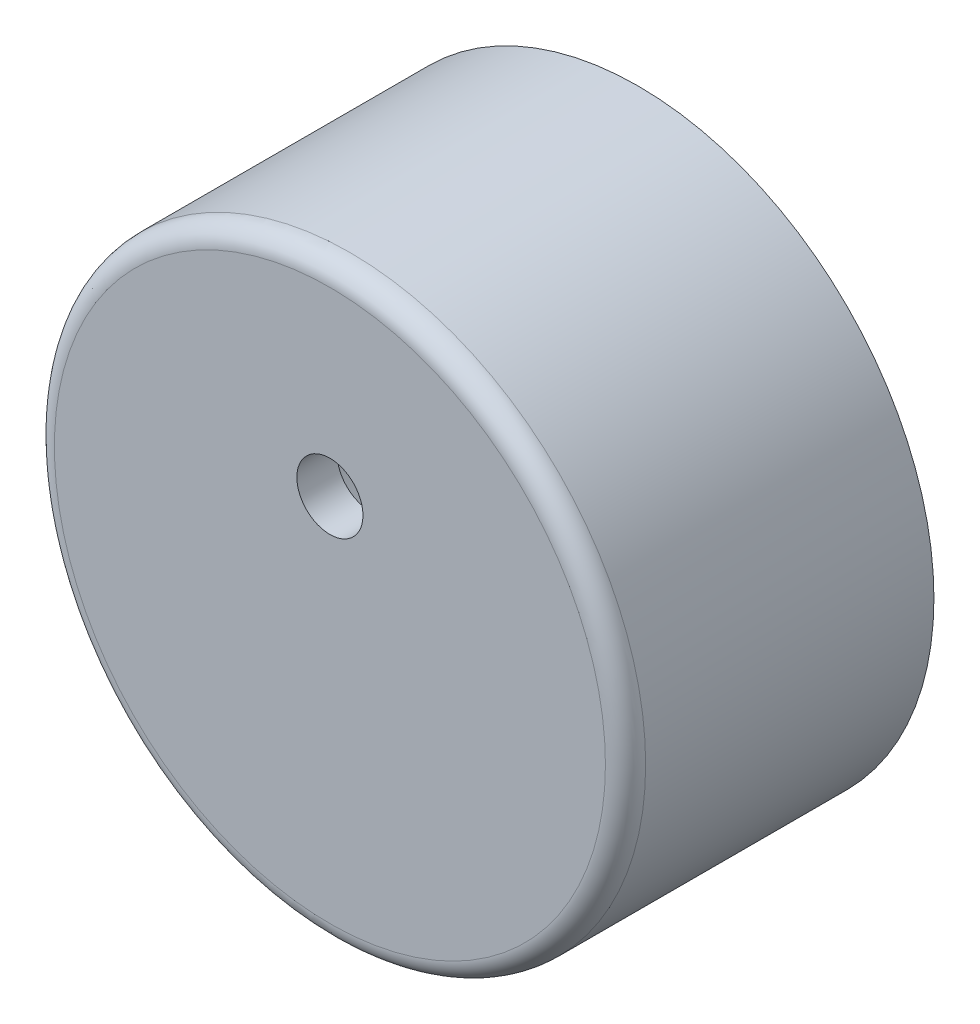
SolidWorks part; units mm, degrees
ref_plane "Front Plane" through (0, 0, 0) normal (0, 0, 1) x (1, 0, 0)
ref_plane "Top Plane" through (0, 0, 0) normal (0, 1, 0) x (1, 0, 0)
ref_plane "Right Plane" through (0, 0, 0) normal (1, 0, 0) x (0, 0, -1)
sketch "Sketch2" plane through (0, 0, 0) normal (0, 0, 1) x (1, 0, 0)
  circle A1 centre (177.5651, -76.6062) radius 41.1
  circle A2 centre (177.5651, -76.6062) radius 44.1
  dimension "D1" = 82.2
  dimension "D2" = 3
extrude "Boss-Extrude1" add sketch "Sketch2" along normal blind 40
sketch "Sketch3" plane through (0, 0, 40) normal (0, 0, 1) x (1, 0, 0)
  circle A0 centre (177.5651, -76.6062) radius 44.1 construction
  circle A1 centre (177.5651, -76.6062) radius 44.1
extrude "Boss-Extrude2" add sketch "Sketch3" along normal blind 6
fillet "Fillet1" radius 7 1 edges at (218.6651, -76.6062, 40)
fillet "Fillet2" radius 3 1 edges at (221.6651, -76.6062, 46)
sketch "skeleton" plane through (0, 0, 0) normal (0, 0, 1) x (1, 0, 0)
  line L0 (177.5651, -35.5062) -> (177.5651, -117.7062) construction
  line L2 (218.6651, -76.6062) -> (136.4651, -76.6062) construction
  circle A0 centre (177.5651, -76.6062) radius 41.1 construction
  circle A1 centre (177.5651, -62.5062) radius 4.93
  circle A2 centre (177.5651, -62.5062) radius 6.93
  dimension "D2" = 9.86
  dimension "D3" = 2
  dimension "D1" = 27
ref_plane "Plane1" through (0, 0, 61) normal (0, 0, 1) x (1, 0, 0)
sketch "Sketch5" plane through (0, 0, 61) normal (0, 0, 1) x (1, 0, 0)
  circle A4 centre (177.5651, -57.2312) radius 3.25
  circle A5 centre (177.5651, -57.2312) radius 4.25
  dimension "D1" = 6.5
  dimension "D2" = 8.5
sketch "Sketch7" plane through (0, 0, 46) normal (0, 0, 1) x (1, 0, 0)
  circle A0 centre (177.5651, -62.5062) radius 6.93 construction
  circle A1 centre (177.5651, -62.5062) radius 6.93
  circle A2 centre (177.5651, -62.5062) radius 4.93 construction
  circle A3 centre (177.5651, -62.5062) radius 4.93
loft "Loft2" add section "Sketch7" section "Sketch5" connector at (180.1364, -56.0709, 46) connector at (181.5565, -55.7715, 61)
loft "Cut-Loft2" cut section "Sketch7<4>" section "Sketch5<6>" connector at (178.0414, -57.5992, 46) connector at (180.7863, -56.7995, 61)
sketch "Sketch7<4>" plane through (0, 0, 46) normal (0, 0, 1) x (1, 0, 0) same geometry as "Sketch7"
sketch "Sketch5<6>" plane through (0, 0, 61) normal (0, 0, 1) x (1, 0, 0) same geometry as "Sketch5"
extrude "Cut-Extrude1" cut sketch "Sketch7<5>" against normal up to next (6 mm away) contours A3 region at (177.5651, -62.5062, 46)
sketch "Sketch7<5>" plane through (0, 0, 46) normal (0, 0, 1) x (1, 0, 0) same geometry as "Sketch7"
delete or keep bodies "Body-Delete/Keep 1" type delete bodies bodies 108
